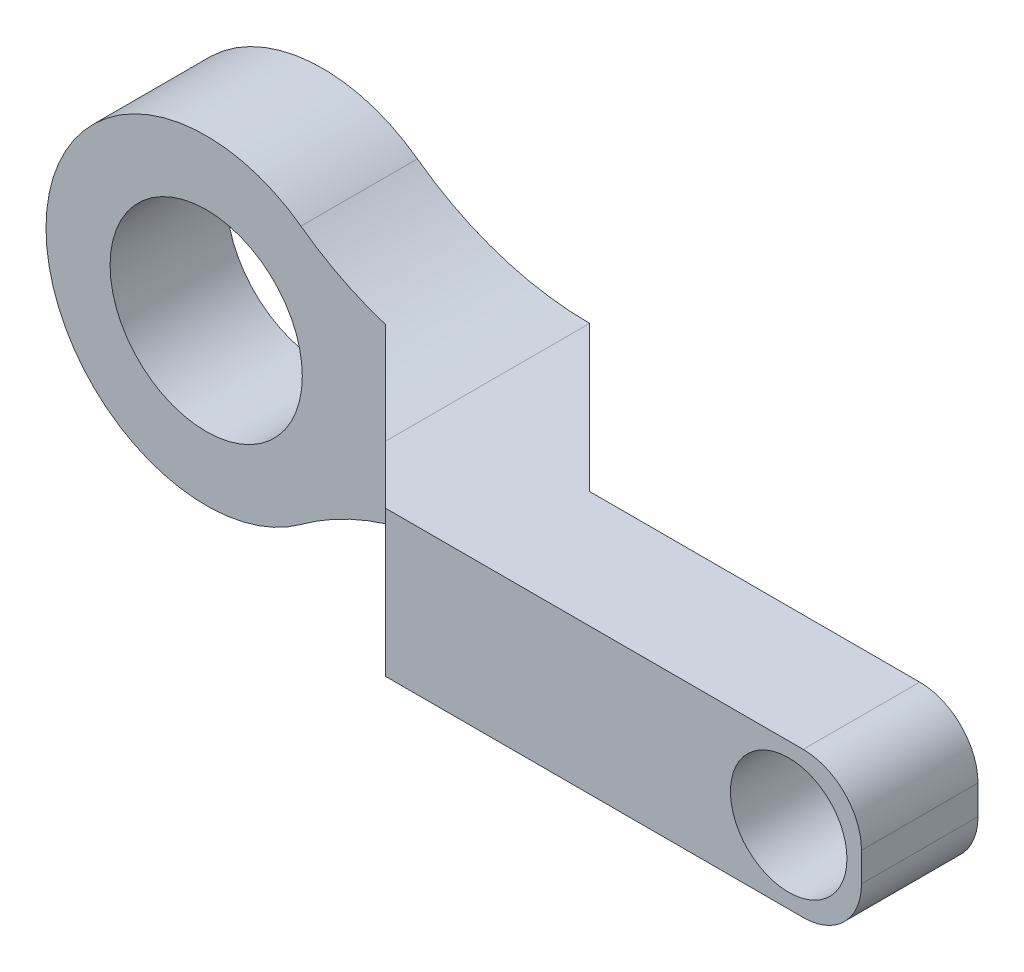
SolidWorks part; units mm, degrees
ref_plane "正面" through (0, 0, 0) normal (0, 0, 1) x (1, 0, 0)
ref_plane "平面" through (0, 0, 0) normal (0, 1, 0) x (1, 0, 0)
ref_plane "右側面" through (0, 0, 0) normal (1, 0, 0) x (0, 0, -1)
sketch "ｽｹｯﾁ1" plane through (0, 0, 0) normal (0, 0, 1) x (1, 0, 0)
  line L1 (2.5, -2.5) -> (-27.5, -2.5)
  line L2 (2.5, -2.5) -> (2.5, 2.5)
  line L3 (2.5, 2.5) -> (-27.5, 2.5)
  line L4 (-27.5, -2.5) -> (-27.5, 2.5)
  circle A1 centre (0, 0) radius 2
  circle A7 centre (-25, 0) radius 5.5
  circle A8 centre (-25, 0) radius 3.3
  point P7 (2.5, 0)
  dimension "D1" = 2.5
  dimension "D3" = 25
  dimension "D5" = 4
  dimension "D6" = 11
  dimension "D9" = 6.6
  dimension "D2" = 2.5
  dimension "D4" = 5
  dimension "D7" = 2.5
  dimension "D8" = 2.5
extrude "ﾎﾞｽ - 押し出し1" add sketch "ｽｹｯﾁ1" along normal blind 4 contours A8 L3 L4 | A8 L4 L1 | A8 L3 A7 L1 L4 | A8 L1 A7 L3 | A7 L1 L2 L3 A1 region at (-9.6965, 0, 0) region at (-30.3486, 0, 0) region at (-20.8897, 0, 0) region at (-27.3876, -2.3876, 0) region at (-27.3876, 2.3876, 0)
fillet "ﾌｨﾚｯﾄ1" radius 10 2 edges at (-20.101, 2.5, 2) (-20.101, -2.5, 2)
fillet "ﾌｨﾚｯﾄ2" radius 2 2 edges at (2.5, 2.5, 2) (2.5, -2.5, 2)
sketch "ｽｹｯﾁ2" plane through (0, 0, 4) normal (0, 0, 1) x (1, 0, 0)
  circle A0 centre (0, 0) radius 13.5
  dimension "D1" = 27
extrude "ﾎﾞｽ - 押し出し2" [suppressed] add sketch "ｽｹｯﾁ2" against normal blind 4
sketch "ｽｹｯﾁ3" [suppressed] plane through (0, 0, 4) normal (0, 0, 1) x (1, 0, 0)
  circle A0 centre (0, 0) radius 12.5
  circle A1 centre (0, 0) radius 12.31
  circle A2 centre (0, 0) radius 11.25
  dimension "D1" = 25
  dimension "D2" = 24.62
  dimension "D3" = 22.5
sketch "ｽｹｯﾁ4" [suppressed] plane through (0, 0, 4) normal (0, 0, 1) x (1, 0, 0)
  line L0 (0, 0) -> (12.31, 0) construction
  circle A1 centre (0, 0) radius 12.31 construction
  spline S0 degree 4 poles (12.31, 0) (12.3485, 0.0017) (12.4561, 0.0115) (12.6589, 0.0505) (12.9814, 0.1425) (13.3857, 0.3027) (13.8844, 0.5544) (14.4379, 0.9043) (15.0083, 1.3425) (15.5792, 1.8672) (16.1068, 2.4351) (16.592, 3.0395) (17.0579, 3.7061) (17.5786, 4.5682) (18.1139, 5.644) (18.6167, 6.9464) (19.0299, 8.4415) (19.3042, 9.968) (19.4462, 11.5121) (19.4619, 13.0627) (19.3579, 14.6092) (19.1396, 16.1446) (18.8138, 17.659) (18.4648, 18.8709) (18.1526, 19.7847) (17.911, 20.4224) (17.7728, 20.7723) (17.6392, 21.0918) (17.5553, 21.2895) (17.4406, 21.5482) (17.3448, 21.7631) (17.1818, 22.1143) (16.9261, 22.6413) (16.6594, 23.1497) (16.4169, 23.5967) (16.2722, 23.8456) (16.1891, 23.9906) knots 0 0 0 0 0 0.005604 0.015718 0.02996 0.048734 0.068727 0.096889 0.125051 0.153212 0.181374 0.209535 0.237696 0.271429 0.327752 0.384075 0.440398 0.496721 0.553044 0.609367 0.66569 0.722013 0.778336 0.834659 0.84874 0.86282 0.876901 0.890982 0.895509 0.900036 0.909091 0.931818 0.954545 0.977273 1 1 1 1 1 construction
  spline S1 degree 4 poles (12.31, 0) (12.3485, 0.0017) (12.4561, 0.0115) (12.6589, 0.0505) (12.9814, 0.1425) (13.3857, 0.3027) (13.8844, 0.5544) (14.4379, 0.9043) (15.0083, 1.3425) (15.5792, 1.8672) (16.1068, 2.4351) (16.592, 3.0395) (17.0579, 3.7061) (17.5786, 4.5682) (18.1139, 5.644) (18.6167, 6.9464) (19.0299, 8.4415) (19.3042, 9.968) (19.4462, 11.5121) (19.4619, 13.0627) (19.3579, 14.6092) (19.1396, 16.1446) (18.8138, 17.659) (18.4648, 18.8709) (18.1526, 19.7847) (17.911, 20.4224) (17.7728, 20.7723) (17.6392, 21.0918) (17.5553, 21.2895) (17.4406, 21.5482) (17.3981, 21.6435) (17.3642, 21.7184) (17.3406, 21.7699) knots 0 0 0 0 0 0.005604 0.015718 0.02996 0.048734 0.068727 0.096889 0.125051 0.153212 0.181374 0.209535 0.237696 0.271429 0.327752 0.384075 0.440398 0.496721 0.553044 0.609367 0.66569 0.722013 0.778336 0.834659 0.84874 0.86282 0.876901 0.890982 0.895509 0.900036 0.909091 0.909091 0.909091 0.909091 0.909091
sketch "ｽｹｯﾁ7" [suppressed] plane through (0, 0, 4) normal (0, 0, 1) x (1, 0, 0)
  line L0 (12.31, 0) -> (0, 0) construction
  line L1 (0, 0) -> (13.4745, -0.8288) construction
  line L2 (11.2288, -0.6907) -> (13.4745, -0.8288) construction
  line L3 (12.31, 0) -> (11.25, 0)
  line L4 (12.2172, -1.5087) -> (11.1652, -1.3787)
  arc A0 (-13.1624, -3) -> (-13.1624, 3) centre (0, 0) ccw construction
  circle A1 centre (0, 0) radius 12.5 construction
  circle A2 centre (0, 0) radius 11.25 construction
  arc A3 (13.3488, -2.015) -> (13.4951, 0.3638) centre (0, 0) ccw
  arc A4 (12.4764, -0.7674) -> (12.5, 0.0221) centre (0, 0) ccw construction
  arc A5 (11.1652, -1.3787) -> (11.25, 0) centre (0, 0) ccw
  spline S0 degree 4 poles (3.7202, 1999.7927) (4.6456, 54.1956) (7.8751, 1.0188) (10.6455, -0.5236) (12.9814, 0.1425) (13.3857, 0.3027) (13.8844, 0.5544) (14.4379, 0.9043) (15.0083, 1.3425) (15.5792, 1.8672) (16.1068, 2.4351) (16.592, 3.0395) (17.0579, 3.7061) (17.5786, 4.5682) (18.1139, 5.644) (18.6167, 6.9464) (19.0299, 8.4415) (19.3042, 9.968) (19.4462, 11.5121) (19.4619, 13.0627) (19.3579, 14.6092) (19.1396, 16.1446) (18.8138, 17.659) (18.4648, 18.8709) (18.1526, 19.7847) (17.911, 20.4224) (17.7728, 20.7723) (17.6392, 21.0918) (17.5553, 21.2895) (16.7643, 23.0728) (18.9302, 18.1286) (-24.8632, 113.3738) (849.1075, -1796.9384) knots -0.304242 -0.304242 -0.304242 -0.304242 -0.304242 0.005604 0.015718 0.02996 0.048734 0.068727 0.096889 0.125051 0.153212 0.181374 0.209535 0.237696 0.271429 0.327752 0.384075 0.440398 0.496721 0.553044 0.609367 0.66569 0.722013 0.778336 0.834659 0.84874 0.86282 0.876901 0.890982 0.895509 0.900036 1.098806 1.098806 1.098806 1.098806 1.098806 only from (12.31, 0) to (17.3406, 21.7699) construction
  spline S1 degree 4 poles (12.31, 0) (12.3485, 0.0017) (12.4561, 0.0115) (12.6589, 0.0505) (12.9589, 0.1361) (13.214, 0.2348) (13.3998, 0.3182) (13.4951, 0.3638) knots 0 0 0 0 0 0.005604 0.015718 0.02996 0.04533 0.04533 0.04533 0.04533 0.04533
  spline S2 degree 4 poles (12.2172, -1.5087) (12.2552, -1.515) (12.3608, -1.538) (12.5573, -1.6016) (12.8445, -1.7232) (13.0856, -1.8525) (13.2598, -1.958) (13.3488, -2.015) knots 0 0 0 0 0 0.005604 0.015718 0.02996 0.04533 0.04533 0.04533 0.04533 0.04533
  point P165 (0, 0)
  dimension "D1" = 0.79
extrude "ｶｯﾄ - 押し出し2" [suppressed] cut sketch "ｽｹｯﾁ7" against normal blind 4
pattern_circular "円形ﾊﾟﾀｰﾝ18" [suppressed] count 25 over 360 of bodies 107
sketch "ｽｹｯﾁ8" plane through (0, 0, 0) normal (0, 0, -1) x (-1, 0, 0)
  line L1 (15.8348, 2.5) -> (15.8348, -2.5)
  circle A0 centre (25, 0) radius 3.3
  circle A1 centre (25, 0) radius 5.5 construction
  circle A2 centre (25, 0) radius 3.3 construction
  arc A3 (21.7478, -4.4355) -> (21.7478, 4.4355) centre (25, 0) ccw construction
  arc A4 (21.7478, 4.4355) -> (15.8348, 2.5) centre (15.8348, 12.5) cw
  arc A5 (21.7478, -4.4355) -> (15.8348, -2.5) centre (15.8348, -12.5) ccw
  arc A6 (21.7478, -4.4355) -> (15.8348, -2.5) centre (15.8348, -12.5) ccw construction
  arc A7 (15.8348, 2.5) -> (21.7478, 4.4355) centre (15.8348, 12.5) ccw construction
  arc A8 (21.7478, 4.4355) -> (21.7478, -4.4355) centre (25, 0) cw
extrude "ﾎﾞｽ - 押し出し3" add sketch "ｽｹｯﾁ8" along normal blind 5
chamfer "面取り1" distance 5 angle 45 1 edges at (-15.8348, 0, 0)
sketch "ｽｹｯﾁ9" plane through (0, 0, 4) normal (0, 0, 1) x (1, 0, 0)
  line L0 (-18.8348, -2.9606) -> (-18.8348, 2.9606)
  line L1 (0.5, -2.5) -> (-15.8348, -2.5) construction
  circle A0 centre (-25, 0) radius 3.3
  circle A1 centre (-25, 0) radius 5.5 construction
  circle A2 centre (-25, 0) radius 3.3 construction
  arc A3 (-21.7478, 4.4355) -> (-21.7478, -4.4355) centre (-25, 0) ccw construction
  arc A4 (-15.8348, -2.5) -> (-21.7478, -4.4355) centre (-15.8348, -12.5) ccw construction
  arc A5 (-21.7478, -4.4355) -> (-18.8348, -2.9606) centre (-15.8348, -12.5) cw
  arc A6 (-21.7478, 4.4355) -> (-18.8348, 2.9606) centre (-15.8348, 12.5) ccw
  arc A7 (-21.7478, 4.4355) -> (-15.8348, 2.5) centre (-15.8348, 12.5) ccw construction
  arc A8 (-21.7478, -4.4355) -> (-21.7478, 4.4355) centre (-25, 0) cw
  dimension "D1" = 3
extrude "ｶｯﾄ - 押し出し3" cut sketch "ｽｹｯﾁ9" against normal blind 5
chamfer "面取り2" distance 5 angle 45 1 edges at (-18.8348, 0, 4)
equation "\"m\"= 1"
equation "\"a\"= 20"
equation "\"z\"= 25"
equation "\"d\"= \"z\" * \"m\""
equation "\"db\"= \"d\" * cos ( \"a\" )"
equation "\"da\"= \"d\" + 2 * \"m\""
equation "\"df\"= \"d\" - 2.5 * \"m\""
equation "\"p\"= PI * \"m\" / 4"
